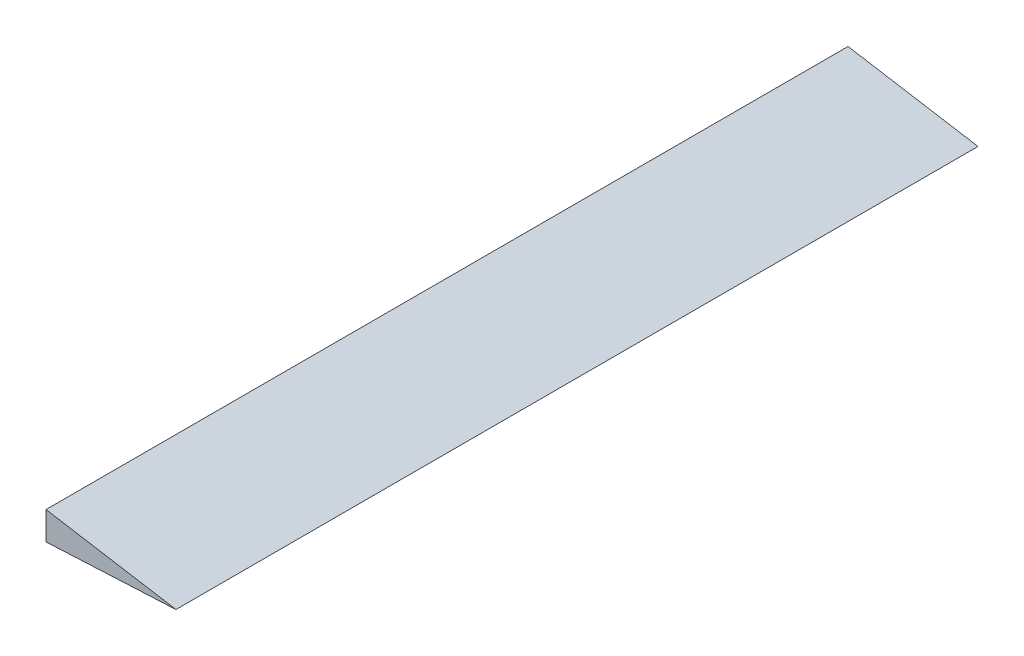
SolidWorks part; units mm, degrees
material "Balsa"
ref_plane "Front Plane" through (0, 0, 0) normal (0, 0, 1) x (1, 0, 0)
ref_plane "Top Plane" through (0, 0, 0) normal (0, 1, 0) x (1, 0, 0)
ref_plane "Right Plane" through (0, 0, 0) normal (1, 0, 0) x (0, 0, -1)
sketch "Sketch1" plane through (0, 0, 0) normal (0, 0, 1) x (1, 0, 0)
  line L0 (306.8496, -2.5161) -> (306.8496, 8.4499) construction
  line L1 (306.8496, -2.5161) -> (306.8496, 8.4499)
  line L2 (306.8496, 8.4499) -> (357.6496, 0)
  line L3 (306.8496, -2.5161) -> (357.6496, 0)
  spline S0 degree 3 poles (354.9573, 0.0431) (358.3317, -0.0432) (354.9981, 0.2938) (352.3707, 0.8024) (346.1763, 1.8676) (338.7813, 3.2655) (329.3081, 4.8919) (318.2482, 6.6648) (305.5952, 8.6507) (291.564, 10.8193) (276.34, 13.1505) (260.1392, 15.5903) (243.1815, 18.0913) (225.699, 20.6027) (207.9209, 23.0318) (190.087, 25.3152) (172.4086, 27.3328) (155.0467, 28.9096) (138.1258, 29.947) (121.7437, 30.3922) (105.9899, 30.2108) (90.9433, 29.4155) (76.6903, 28.0308) (63.3272, 26.1868) (50.9728, 23.9485) (39.7523, 21.3791) (29.7714, 18.545) (21.1318, 15.5018) (13.8914, 12.3237) (8.1391, 9.1075) (3.8158, 5.9031) (1.1802, 2.9693) (-0.4877, -0.018) (1.2572, -2.9285) (4.805, -4.6528) (9.8754, -6.6365) (16.78, -8.2511) (25.3535, -9.7017) (35.5828, -10.8813) (47.3622, -11.8027) (60.5842, -12.4624) (75.1117, -12.8607) (90.7897, -13.0132) (107.4435, -12.9137) (124.9052, -12.5651) (143.0256, -11.8868) (161.6617, -10.9405) (180.6424, -9.8572) (199.7442, -8.7119) (218.721, -7.5525) (237.3263, -6.4253) (255.3201, -5.3536) (272.4652, -4.367) (288.5372, -3.4753) (303.3148, -2.6922) (316.6121, -2.0207) (328.2104, -1.4385) (338.1246, -0.9102) (345.8395, -0.4061) (352.2525, -0.129) (354.9573, 0.0431) (358.3317, -0.0432) (354.9981, 0.2938) knots -0.015092 -0.006889 -0.001754 0 0.001748 0.006827 0.01488 0.025572 0.038694 0.054171 0.071834 0.091435 0.112685 0.135293 0.158944 0.183315 0.20807 0.232879 0.257399 0.281384 0.304706 0.327241 0.348897 0.369607 0.389308 0.407886 0.425177 0.441027 0.4553 0.467904 0.478752 0.487814 0.49509 0.500617 0.504451 0.507804 0.513091 0.520546 0.530249 0.542214 0.556382 0.572656 0.590895 0.610925 0.632536 0.655496 0.679547 0.704499 0.730211 0.756436 0.782837 0.809062 0.834776 0.859641 0.883338 0.905541 0.925965 0.944326 0.960366 0.973929 0.984908 0.993111 0.998246 1 1.001748 1.006827 1.01488 only from (357.6496, 0) to (357.6496, 0) construction
  spline S1 degree 3 poles (354.9573, 0.0431) (358.3317, -0.0432) (354.9981, 0.2938) (352.3707, 0.8024) (346.1763, 1.8676) (338.7813, 3.2655) (329.3081, 4.8919) (318.2482, 6.6648) (305.5952, 8.6507) (291.564, 10.8193) (276.34, 13.1505) (260.1392, 15.5903) (243.1815, 18.0913) (225.699, 20.6027) (207.9209, 23.0318) (190.087, 25.3152) (172.4086, 27.3328) (155.0467, 28.9096) (138.1258, 29.947) (121.7437, 30.3922) (105.9899, 30.2108) (90.9433, 29.4155) (76.6903, 28.0308) (63.3272, 26.1868) (50.9728, 23.9485) (39.7523, 21.3791) (29.7714, 18.545) (21.1318, 15.5018) (13.8914, 12.3237) (8.1391, 9.1075) (3.8158, 5.9031) (1.1802, 2.9693) (-0.4877, -0.018) (1.2572, -2.9285) (4.805, -4.6528) (9.8754, -6.6365) (16.78, -8.2511) (25.3535, -9.7017) (35.5828, -10.8813) (47.3622, -11.8027) (60.5842, -12.4624) (75.1117, -12.8607) (90.7897, -13.0132) (107.4435, -12.9137) (124.9052, -12.5651) (143.0256, -11.8868) (161.6617, -10.9405) (180.6424, -9.8572) (199.7442, -8.7119) (218.721, -7.5525) (237.3263, -6.4253) (255.3201, -5.3536) (272.4652, -4.367) (288.5372, -3.4753) (303.3148, -2.6922) (316.6121, -2.0207) (328.2104, -1.4385) (338.1246, -0.9102) (345.8395, -0.4061) (352.2525, -0.129) (354.9573, 0.0431) (358.3317, -0.0432) (354.9981, 0.2938) knots -0.015092 -0.006889 -0.001754 0 0.001748 0.006827 0.01488 0.025572 0.038694 0.054171 0.071834 0.091435 0.112685 0.135293 0.158944 0.183315 0.20807 0.232879 0.257399 0.281384 0.304706 0.327241 0.348897 0.369607 0.389308 0.407886 0.425177 0.441027 0.4553 0.467904 0.478752 0.487814 0.49509 0.500617 0.504451 0.507804 0.513091 0.520546 0.530249 0.542214 0.556382 0.572656 0.590895 0.610925 0.632536 0.655496 0.679547 0.704499 0.730211 0.756436 0.782837 0.809062 0.834776 0.859641 0.883338 0.905541 0.925965 0.944326 0.960366 0.973929 0.984908 0.993111 0.998246 1 1.001748 1.006827 1.01488 only from (357.6496, 0) to (357.6496, 0)
sketch "Sketch2" plane through (0, 0, -761.9997) normal (0, 0, -1) x (-1, 0, 0)
  line L0 (-306.8496, -2.5161) -> (-306.8496, 8.4499) construction
  line L1 (-306.8496, -2.5161) -> (-357.6496, 0) construction
  line L2 (-306.8496, 8.4499) -> (-357.6496, 0) construction
  line L3 (-306.8496, -2.5161) -> (-306.8496, 8.4499)
  line L4 (-306.8496, -2.5161) -> (-357.6496, 0)
  line L5 (-306.8496, 8.4499) -> (-357.6496, 0)
extrude "Boss-Extrude2" add sketch "Sketch2" against normal blind 313.5173
sketch "Sketch3" plane through (306.8496, 0, 0) normal (-1, 0, 0) x (0, 0, 1)
  line L0 (-761.9997, -2.5161) -> (-761.9997, 8.4499) construction
  line L1 (-448.4825, -2.5161) -> (-448.4825, 8.4499) construction
  point P0 (-761.9997, 2.9669)
  point P1 (-448.4825, 2.9669)
